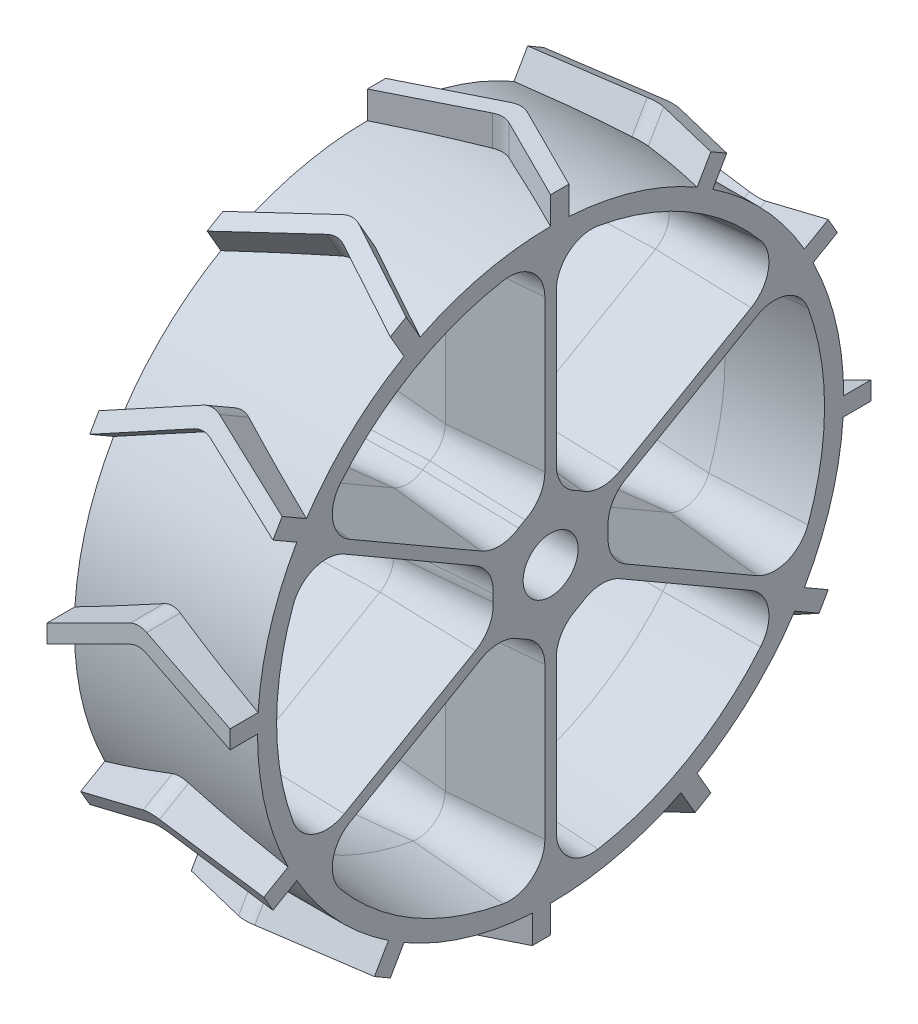
SolidWorks part; units mm, degrees
ref_plane "Front Plane" through (0, 0, 0) normal (0, 0, 1) x (1, 0, 0)
ref_plane "Top Plane" through (0, 0, 0) normal (0, 1, 0) x (1, 0, 0)
ref_plane "Right Plane" through (0, 0, 0) normal (1, 0, 0) x (0, 0, -1)
sketch "Sketch2" plane through (0, 0, 0) normal (1, 0, 0) x (0, 0, -1)
  circle A2 centre (0, 0) radius 159.9966
extrude "Boss-Extrude1" add sketch "Sketch2" along normal blind 100
sketch "Sketch4" plane through (0, 0, 0) normal (0, 1, 0) x (1, 0, 0)
  line L8 (0, 0) -> (100, 0) construction
  line L9 (100, -159.9966) -> (100, 159.9966) construction
  line L10 (0, 0) -> (45.5279, 22.7639)
  line L11 (54.4721, 22.7639) -> (100, 0)
  line L12 (100, 0) -> (100, 10)
  line L13 (100, 10) -> (54.4721, 32.7639)
  line L14 (45.5279, 32.7639) -> (0, 10)
  line L15 (0, 159.9966) -> (0, -159.9966) construction
  line L16 (0, 10) -> (0, 0)
  arc A0 (54.4721, 32.7639) -> (45.5279, 32.7639) centre (50, 23.8197) ccw
  arc A1 (45.5279, 22.7639) -> (54.4721, 22.7639) centre (50, 13.8197) cw
  point P4 (50, 0)
  point P18 (50, 35)
  point P21 (50, 25)
  dimension "D3" = 10
  dimension "D1" = 10
  dimension "D2" = 10
  dimension "D4" = 25
extrude "Boss-Extrude2" add sketch "Sketch4" along normal blind 175
pattern_circular "CirPattern2" count 12 over 360 about axis through (100, 0, 0) along (-1, 0, 0) of "Boss-Extrude2"
sketch "Sketch5" plane through (0, 0, 0) normal (-1, 0, 0) x (0, 0, 1)
  line L0 (0, 0) -> (0, 159.9966) construction
  line L1 (0, 0) -> (138.5611, 79.9983) construction
  line L6 (7.5, 128.2314) -> (7.5, 45.5394)
  line L8 (107.3017, 70.6109) -> (35.6883, 29.2649)
  arc A0 (159.6838, 10) -> (138.5611, 79.9983) centre (0, 0) ccw construction
  arc A2 (25.0924, 143.0057) -> (111.3004, 93.2335) centre (0, 0) cw
  arc A5 (15.8556, 32.0913) -> (19.8641, 29.777) centre (0, 0) cw
  arc A6 (111.3004, 93.2335) -> (107.3017, 70.6109) centre (99.8017, 83.6013) cw
  arc A7 (25.0924, 143.0057) -> (7.5, 128.2314) centre (22.5, 128.2314) ccw
  arc A8 (19.8641, 29.777) -> (35.6883, 29.2649) centre (28.1883, 42.2553) ccw
  arc A9 (7.5, 45.5394) -> (15.8556, 32.0913) centre (22.5, 45.5394) ccw
  point P4 (25.9808, 15)
  point P8 (0, 35)
  point P9 (125.5707, 72.4983)
  point P10 (17.887, 25.2251)
  point P11 (0, 144.9966)
  point P12 (121.8552, 78.9403)
  point P22 (7.5, 144.9966)
  point P27 (7.5, 35)
  dimension "D1" = 15
  dimension "D2" = 7.5
  dimension "D3" = 7.5
  dimension "D8" = 15
  dimension "D4" = 35
  dimension "D5" = 15
  dimension "D6" = 30
  dimension "D7" = 7.5
  dimension "D9" = 60
extrude "Cut-Extrude3" cut sketch "Sketch5" against normal up to next
chamfer "Chamfer11" distance 50 angle 5 8 edges at (100, 27.2631, 27.7031) (100, 49.9379, 71.495) (100, 30.999, 17.8973) (100, 80.9904, 114.5727) (100, 37.6232, 9.759) (100, 125.7386, 72.5952) (100, 86.8854, 7.5) (100, 139.7181, 12.8534) first distance on face at (50, 28.392, 27.7396) first distance on face at (50, 49.9379, 71.495) first distance on face at (50, 30.9666, 17.8786) first distance on face at (50, 81.4563, 111.9369) first distance on face at (50, 38.2192, 10.7184) first distance on face at (50, 121.9291, 70.3958) first distance on face at (50, 86.8854, 7.5) first distance on face at (50, 137.6683, 14.5748)
chamfer "Chamfer14" distance 50 angle 5 8 edges at (0, 27.2631, 27.7031) (0, 49.9379, 71.495) (0, 30.999, 17.8973) (0, 80.9904, 114.5727) (0, 37.6232, 9.759) (0, 125.7386, 72.5952) (0, 86.8854, 7.5) (0, 139.7181, 12.8534) first distance on face at (25, 28.392, 27.7396) first distance on face at (25, 49.9379, 71.495) first distance on face at (25, 30.9666, 17.8786) first distance on face at (25, 81.4563, 111.9369) first distance on face at (25, 38.2192, 10.7184) first distance on face at (25, 121.9291, 70.3958) first distance on face at (25, 86.8854, 7.5) first distance on face at (25, 137.6683, 14.5748)
pattern_circular "CirPattern7" count 6 over 360 about axis through (0, 0, 0) along (1, 0, 0) of "Cut-Extrude3", "Chamfer11", "Chamfer14"
sketch "Sketch6" plane through (0, 0, 0) normal (-1, 0, 0) x (0, 0, 1)
  circle A0 centre (0, 0) radius 15
extrude "Cut-Extrude4" cut sketch "Sketch6" against normal up to next
